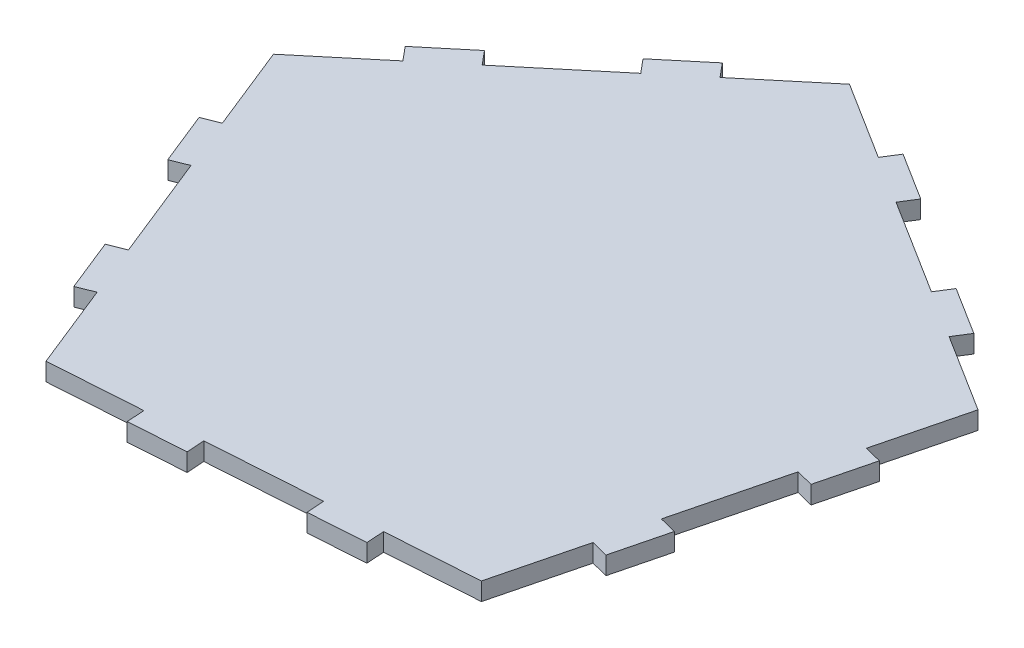
SolidWorks part; units mm, degrees
ref_plane "Front Plane" through (0, 0, 0) normal (0, 0, 1) x (1, 0, 0)
ref_plane "Top Plane" through (0, 0, 0) normal (0, 1, 0) x (1, 0, 0)
ref_plane "Right Plane" through (0, 0, 0) normal (1, 0, 0) x (0, 0, -1)
sketch "Sketch1" plane through (0, 0, 0) normal (0, 1, 0) x (1, 0, 0)
  line L1 (-63.7371, 16.0796) -> (-34.9884, -55.6487)
  line L2 (-34.9884, -55.6487) -> (42.1131, -50.4724)
  line L3 (42.1131, -50.4724) -> (61.0157, 24.4551)
  line L4 (61.0157, 24.4551) -> (-4.4033, 65.5865)
  line L5 (-4.4033, 65.5865) -> (-63.7371, 16.0796)
  circle A0 centre (0, 0) radius 53.18 construction
  dimension "D1" = 106.36
extrude "Boss-Extrude1" add sketch "Sketch1" along normal blind 3.18
sketch "Sketch2" plane through (0, 0, 0) normal (0, -1, 0) x (1, 0, 0)
  line L0 (-56.8852, 1.016) -> (-53.9335, -0.1671)
  line L1 (-56.8852, 1.016) -> (-53.0831, 10.5024)
  line L2 (-53.9335, -0.1671) -> (-50.1313, 9.3193)
  line L3 (-53.0831, 10.5024) -> (-50.1313, 9.3193)
  line L4 (-63.7371, -16.0796) -> (-34.9884, 55.6487) construction
  line L5 (-45.6425, 29.0668) -> (-41.8403, 38.5532)
  line L6 (-45.6425, 29.0668) -> (-42.6907, 27.8837)
  line L7 (-41.8403, 38.5532) -> (-38.8886, 37.3701)
  line L8 (-42.6907, 27.8837) -> (-38.8886, 37.3701)
  line L9 (-49.3628, 19.7846) -> (-19.2439, 7.7129) construction
  dimension "D1" = 3.18
  dimension "D2" = 10.22
  dimension "D3" = 10
extrude "Cut-Extrude1" [suppressed] cut sketch "Sketch2" against normal through all
ref_axis "Axis1" through (0, 3.339, 0) along (0, -1, 0)
pattern_circular "CirPattern1" [suppressed] count 5 over 360 about axis through (0, 3.339, 0) along (0, -1, 0) of bodies 102
sketch "Sketch3" plane through (0, 0, 0) normal (0, -1, 0) x (1, 0, 0)
  line L0 (-56.8034, 1.2202) -> (-53.8516, 0.0371)
  line L1 (-56.8034, 1.2202) -> (-53.0831, 10.5024)
  line L2 (-53.8516, 0.0371) -> (-50.1313, 9.3193)
  line L3 (-53.0831, 10.5024) -> (-50.1313, 9.3193)
  line L4 (-63.7371, -16.0796) -> (-34.9884, 55.6487) construction
  line L5 (-45.6425, 29.0668) -> (-42.6907, 27.8837)
  line L6 (-45.6425, 29.0668) -> (-41.9222, 38.349)
  line L7 (-42.6907, 27.8837) -> (-38.9704, 37.1659)
  line L8 (-41.9222, 38.349) -> (-38.9704, 37.1659)
  line L9 (0, 0) -> (-49.3628, 19.7846) construction
  line L10 (-65.563, -20.6353) -> (-62.6113, -21.8183)
  line L11 (-65.563, -20.6353) -> (-33.4497, 59.4878)
  line L12 (-62.6113, -21.8183) -> (-30.498, 58.3048)
  line L13 (-33.4497, 59.4878) -> (-30.498, 58.3048)
  line M14 (-63.7371, -16.0796) -> (-4.4033, -65.5865)
  line M17 (42.1131, 50.4724) -> (-34.9884, 55.6487)
  line M18 (-34.9884, 55.6487) -> (-63.7371, -16.0796)
  dimension "D1" = 10
  dimension "D2" = 10
  dimension "D3" = 3.18
  dimension "D4" = 3.18
extrude "Cut-Extrude2" cut sketch "Sketch3" against normal blind 10 contours L12 L0 M14 M18 | L12 L9 L11 L3 | L9 L12 L5 M18 | L8 L12 M17 M18 region at (-58.8781, 0, -8.2685) region at (-49.747, 0, 14.5519) region at (-46.0267, 0, 23.8342) region at (-36.8692, 0, 46.6439)
pattern_circular "CirPattern2" count 5 over 360 about axis through (0, 3.339, 0) along (0, -1, 0) of "Cut-Extrude2"
equation "\"kerf\"= .22mm"
equation "\"tabWidth\"= 10 + \"kerf\" "
equation "\"tabSeperation\" = 10  "
equation "\"tabThickness\"= 3.18"
equation "\"D2@Sketch2\"=\"tabWidth\""
equation "\"D1@Sketch2\"=\"tabThickness\""
equation "\"D3@Sketch2\"=\"tabSeperation\""
equation "\"D2@Sketch3\"=\"tabSeperation\""
equation "\"D3@Sketch3\"=\"tabThickness\""
equation "\"D4@Sketch3\"=\"tabThickness\""
equation "\"tabLength\" = \"kerf\" + 12"
